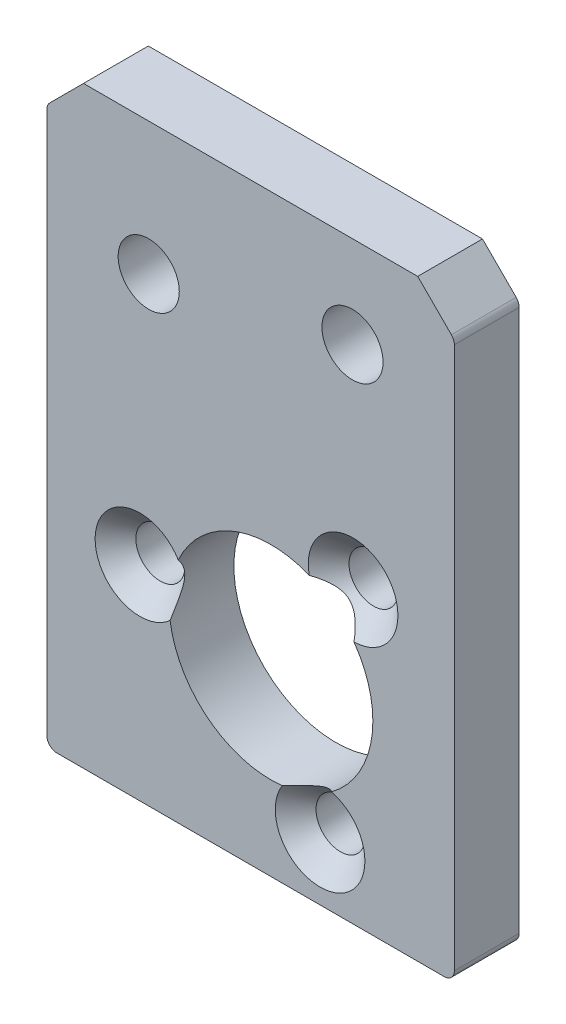
SolidWorks part; units mm, degrees
ref_plane "Front Plane" through (0, 0, 0) normal (0, 0, 1) x (1, 0, 0)
ref_plane "Top Plane" through (0, 0, 0) normal (0, 1, 0) x (1, 0, 0)
ref_plane "Right Plane" through (0, 0, 0) normal (1, 0, 0) x (0, 0, -1)
sketch "Sketch1" plane through (0, 0, 0) normal (0, 0, 1) x (1, 0, 0)
  line L1 (0, 0) -> (20, 0)
  line L2 (0, 0) -> (0, 29.11)
  line L3 (0, 29.11) -> (20, 29.11)
  line L4 (20, 0) -> (20, 29.11)
  circle A0 centre (5, 22.61) radius 1.5
  circle A1 centre (15, 24.61) radius 1.5
  arc A2 (15.0728, 12.0104) -> (12.8801, 13.743) centre (15.03, 14.21) ccw
  arc A3 (6.4499, 11.1828) -> (6.049, 8.4114) centre (4.57, 10.04) ccw
  arc A4 (11.5537, 4.1408) -> (13.9699, 5.0876) centre (13.41, 2.96) ccw
  circle A7 centre (15.03, 14.21) radius 1.2
  circle A8 centre (4.57, 10.04) radius 1.2
  circle A9 centre (13.41, 2.96) radius 1.2
  circle A10 centre (11, 9.11) radius 5
extrude "Boss-Extrude2" add sketch "Sketch1" against normal blind 3.18 contours A0 | A1 | L2 L1 L4 L3 | A7 | A10 | A8 | A9 region at (5, 22.61, 0) region at (15, 24.61, 0)
hole_wizard "CSK for M2 Flat Head Machine Screw1" positions "Sketch10" profile "Sketch11" countersink size "M2" standard "ANSI Metric"
sketch "Sketch10" plane through (0, 0, 0) normal (0, 0, 1) x (1, 0, 0)
  point P0 (4.57, 10.04)
  point P3 (15.03, 14.21)
  point P6 (13.41, 2.96)
sketch "Sketch11" plane through (4.57, 10.04, 0) normal (1, 0, 0) x (0, -1, 0)
  line L0 (0, 0) -> (0, 4.23)
  line L1 (0, 4.23) -> (1.2, 3.509)
  line L2 (1.2, 3.509) -> (1.2, 1)
  line L3 (1.2, 1) -> (2.2, 0)
  line L5 (2.2, 0) -> (0, 0)
  line L6 (-1.2, 1) -> (-2.2, 0) construction
  line L10 (0, 4.23) -> (-1.2, 3.509) construction
  line L11 (0, -6.35) -> (0, 107.95) construction
  dimension "Hole Dia." = 2.4
  dimension "Hole Depth" = 4.23
  dimension "Near C'Sink Dia." = 4.4
  dimension "Near C'Sink Angle" = 90
  dimension "Drill Angle" = 118
chamfer "Chamfer1" distance 1.8 angle 45 2 edges at (0, 29.11, -1.59) (20, 29.11, -1.59)
fillet "Fillet3" radius 0.5 4 edges at (20, 0, -1.59) (0, 0, -1.59) (0, 27.31, -1.59) (20, 27.31, -1.59)
